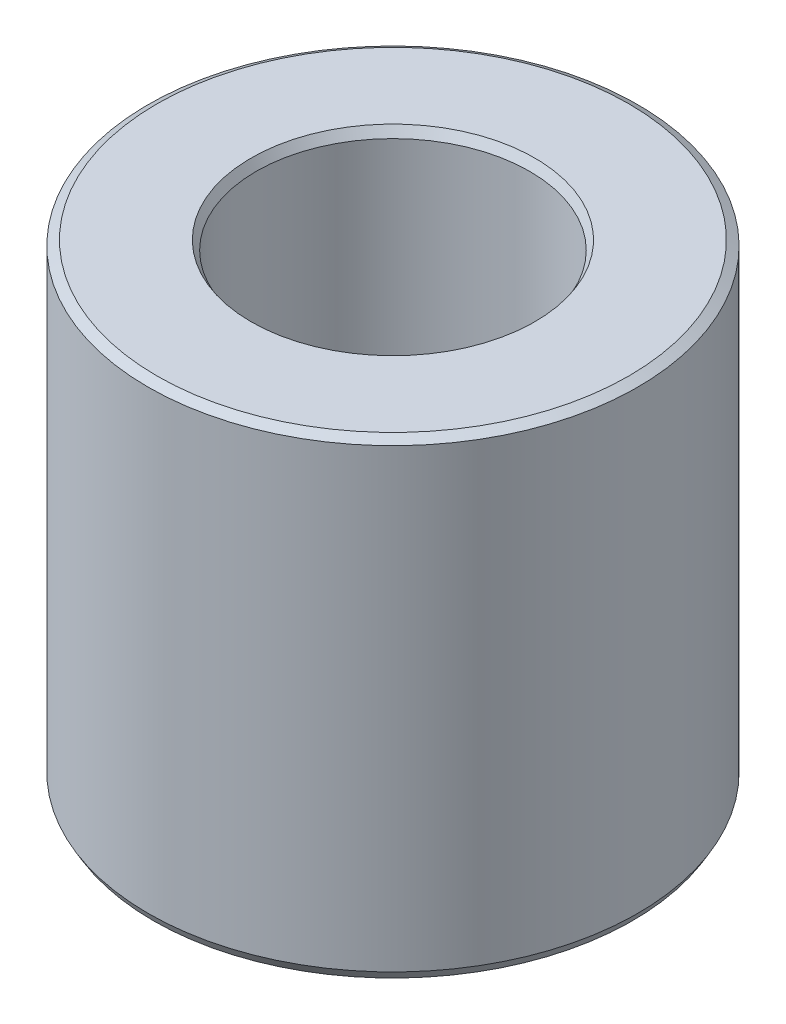
SolidWorks part; units mm, degrees
ref_plane "Front Plane" through (0, 0, 0) normal (0, 0, 1) x (1, 0, 0)
ref_plane "Top Plane" through (0, 0, 0) normal (0, 1, 0) x (1, 0, 0)
ref_plane "Right Plane" through (0, 0, 0) normal (1, 0, 0) x (0, 0, -1)
sketch "Sketch1" plane through (0, 0, 0) normal (0, 1, 0) x (1, 0, 0)
  circle A0 centre (0, 0) radius 10
  dimension "SLEEVE_OD" = 20
extrude "Boss-Extrude1" add sketch "Sketch1" along normal blind 19.1955
sketch "Sketch2" plane through (0, 0, 0) normal (0, 1, 0) x (1, 0, 0)
  circle A0 centre (0, 0) radius 5.5851
  dimension "BORE_D" = 11.1701
extrude "Cut-Extrude1" cut sketch "Sketch2" along normal through all
chamfer "Chamfer1" distance 0.2108 angle 60 4 edges at (0, 19.1955, 5.5851) (0, 0, 5.5851) (0, 0, 10) (0, 19.1955, 10) first distance on face at (0, 19.1955, 5.5851) first distance on face at (0, 0, 5.5851) first distance on face at (0, 19.1955, 10)
